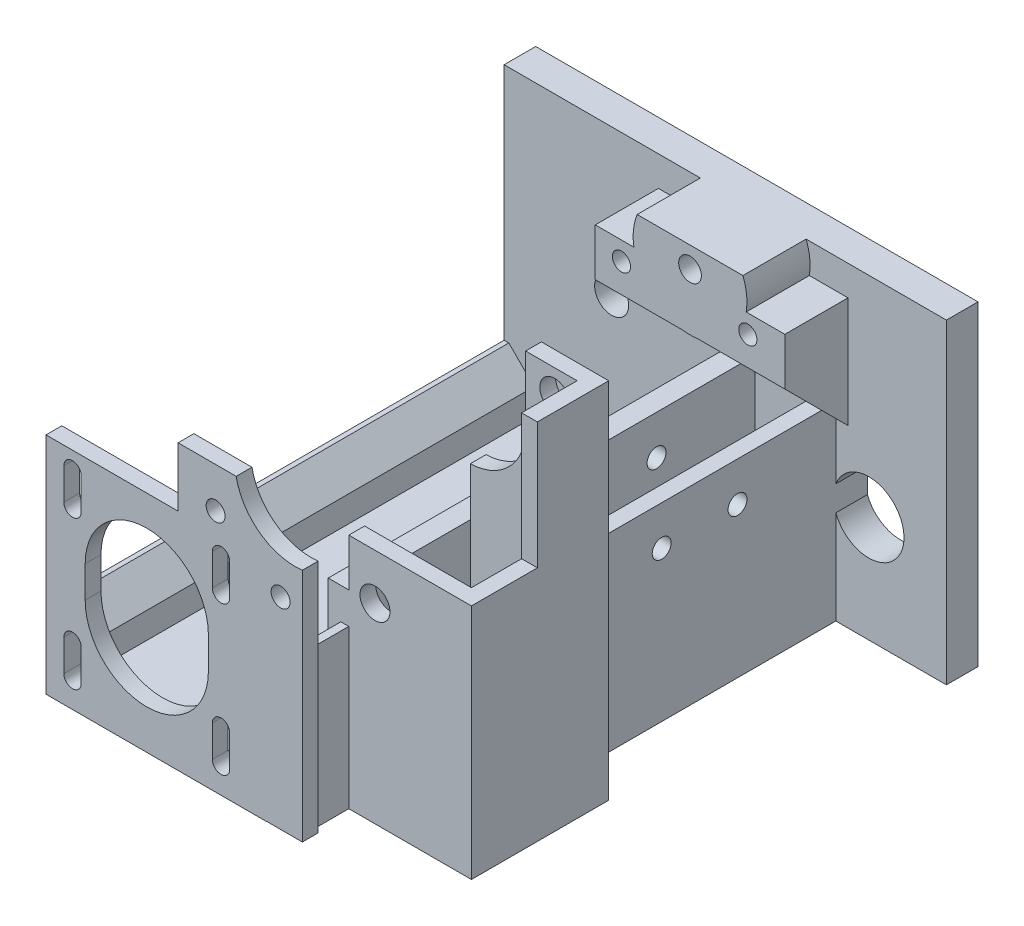
SolidWorks part; units mm, degrees
material "ABS"
ref_plane "Front Plane" through (0, 0, 0) normal (0, 0, 1) x (1, 0, 0)
ref_plane "Top Plane" through (0, 0, 0) normal (0, 1, 0) x (1, 0, 0)
ref_plane "Right Plane" through (0, 0, 0) normal (1, 0, 0) x (0, 0, -1)
sketch "Sketch1" plane through (0, 0, 0) normal (0, 0, 1) x (1, 0, 0)
  line L1 (-65.5446, 32.6733) -> (74.4554, 32.6733)
  line L2 (-65.5446, 32.6733) -> (-65.5446, -67.3267)
  line L3 (-65.5446, -67.3267) -> (74.4554, -67.3267)
  line L4 (74.4554, 32.6733) -> (74.4554, -67.3267)
  dimension "D1" = 100
  dimension "D2" = 140
extrude "Boss-Extrude1" add sketch "Sketch1" along normal blind 10
sketch "Sketch2" plane through (0, 0, 10) normal (0, 0, 1) x (1, 0, 0)
  line L0 (-65.5446, -67.3267) -> (-65.5446, -42.849)
  line L3 (-65.5446, -67.3267) -> (7.3151, -67.3267)
  line L5 (-65.5446, -67.3267) -> (74.4554, -67.3267) construction
  line L8 (-65.5446, 32.6733) -> (-65.5446, -67.3267) construction
  line L9 (-65.5446, -42.849) -> (-56.0483, -42.849)
  line L10 (-56.0483, -42.849) -> (-56.0483, -59.0904)
  line L11 (-56.0483, -59.0904) -> (7.3151, -59.0904)
  line L12 (7.3151, -59.0904) -> (7.3151, -7.3423)
  line L13 (7.3151, -7.3423) -> (13.8255, -7.3423)
  line L14 (13.8255, -7.3423) -> (13.8255, -67.3267)
  line L15 (13.8255, -67.3267) -> (7.3151, -67.3267)
extrude "Boss-Extrude2" add sketch "Sketch2" along normal blind 140
sketch "Sketch3" plane through (0, 0, 10) normal (0, 0, 1) x (1, 0, 0)
  line L1 (-16.6941, 23.1955) -> (43.3059, 23.1955)
  line L2 (-16.6941, 23.1955) -> (-16.6941, 8.1955)
  line L3 (-16.6941, 8.1955) -> (43.3059, 8.1955)
  line L4 (43.3059, 23.1955) -> (43.3059, 8.1955)
  dimension "D1" = 15
  dimension "D2" = 60
extrude "Boss-Extrude3" add sketch "Sketch3" along normal blind 20
sketch "Sketch4" plane through (0, 0, 10) normal (0, 0, 1) x (1, 0, 0)
  line L0 (43.3059, 8.1955) -> (43.3059, 23.1955) construction
  circle A0 centre (13.3059, 26.0432) radius 18
  dimension "D1" = 36
  dimension "D2" = 30
extrude "Boss-Extrude4" add sketch "Sketch4" along normal blind 20
sketch "Sketch6" plane through (0, 0, 30) normal (0, 0, 1) x (1, 0, 0)
  circle A0 centre (13.3059, 26.0432) radius 3.5973
  arc A1 (31.0792, 23.1955) -> (-4.4674, 23.1955) centre (13.3059, 26.0432) ccw construction
extrude "Cut-Extrude2" cut sketch "Sketch6" against normal blind 100
sketch "Sketch5" plane through (0, 0, 30) normal (0, 0, 1) x (1, 0, 0)
  line L0 (74.4554, 32.6733) -> (30.0404, 32.6733) construction
  line L1 (-13.303, 47.4) -> (34.4273, 47.4)
  line L2 (-13.303, 47.4) -> (-13.303, 32.6733)
  line L3 (-13.303, 32.6733) -> (34.4273, 32.6733)
  line L4 (34.4273, 47.4) -> (34.4273, 32.6733)
extrude "Cut-Extrude1" cut sketch "Sketch5" against normal blind 20
sketch "Sketch7" plane through (0, 0, 30) normal (0, 0, 1) x (1, 0, 0)
  circle A0 centre (-8.3949, 17.2978) radius 2.8779
extrude "Cut-Extrude3" cut sketch "Sketch7" against normal blind 100
pattern_linear "LPattern1" count 2 spacing 40 along (1, 0, 0) of "Cut-Extrude3"
sketch "Sketch9" plane through (0, 0, 150) normal (0, 0, 1) x (1, 0, 0)
  line L0 (-65.5446, 32.6733) -> (-65.5446, -42.849) construction
  line L1 (4.1877, 3.7072) -> (-65.5446, 3.7072)
  line L2 (4.1877, 3.7072) -> (4.1877, -67.3896)
  line L3 (4.1877, -67.3896) -> (-65.5446, -67.3896)
  line L4 (-65.5446, 3.7072) -> (-65.5446, -67.3896)
extrude "Boss-Extrude5" add sketch "Sketch9" along normal blind 5
chamfer "Chamfer1" distance 20 angle 45 2 edges at (29.4741, 8.1955, 10) (-2.8623, 8.1955, 10)
sketch "Sketch11" plane through (0, 0, 155) normal (0, 0, 1) x (1, 0, 0)
  line L0 (13.8255, -67.3267) -> (74.4554, -67.3267) construction
  line L1 (-23.7439, 22.4423) -> (15.6103, 22.4423)
  line L2 (-23.7439, 22.4423) -> (-23.7439, -67.3267)
  line L3 (-23.7439, -67.3267) -> (15.6103, -67.3267)
  line L4 (15.6103, 22.4423) -> (15.6103, -67.3267)
extrude "Boss-Extrude6" add sketch "Sketch11" against normal blind 5
sketch "Sketch12" plane through (0, 0, 155) normal (0, 0, 1) x (1, 0, 0)
  circle A0 centre (13.3059, 26.0432) radius 19
extrude "Cut-Extrude5" cut sketch "Sketch12" against normal blind 10
sketch "Sketch13" plane through (0, 0, 155) normal (0, 0, 1) x (1, 0, 0)
  circle A0 centre (-11.8599, 9.7129) radius 3
  circle A1 centre (8.7091, -3.6025) radius 3
  circle A2 centre (13.3059, 26.0432) radius 30 construction
  dimension "D1" = 6
  dimension "D2" = 6
extrude "Cut-Extrude6" cut sketch "Sketch13" against normal blind 10
fillet "Fillet2" radius 10 rebuild error yes
chamfer "Chamfer2" distance 8 angle 45 1 edges at (-56.0483, -42.849, 80)
sketch "Sketch14" plane through (0, 0, 10) normal (0, 0, 1) x (1, 0, 0)
  circle A0 centre (-31.5077, -13.6101) radius 5.3914
  circle A1 centre (49.8779, -33.6888) radius 11.1548
extrude "Cut-Extrude7" cut sketch "Sketch14" against normal blind 10
sketch "Sketch15" plane through (0, -67.3267, 0) normal (0, -1, 0) x (1, 0, 0)
  line L1 (4.5956, 95.0738) -> (52.6384, 95.0738)
  line L2 (4.5956, 95.0738) -> (4.5956, 138.5253)
  line L3 (4.5956, 138.5253) -> (52.6384, 138.5253)
  line L4 (52.6384, 95.0738) -> (52.6384, 138.5253)
extrude "Boss-Extrude7" add sketch "Sketch15" against normal blind 5
sketch "Sketch16" plane through (0, -62.3267, 0) normal (0, 1, 0) x (1, 0, 0)
  line L8 (13.8255, -133.5253) -> (13.8255, -138.5253)
  line L9 (13.8255, -138.5253) -> (13.8255, -95.0738) construction
  line L10 (13.8255, -138.5253) -> (52.6384, -138.5253)
  line L11 (52.6384, -138.5253) -> (52.6384, -116.7995)
  line L12 (52.6384, -95.0738) -> (52.6384, -138.5253) construction
  line L13 (52.6384, -116.7995) -> (47.6384, -116.7995)
  line L14 (47.6384, -116.7995) -> (47.6384, -133.5253)
  line L15 (47.6384, -133.5253) -> (13.8255, -133.5253)
  dimension "D1" = 5
  dimension "D2" = 5
extrude "Boss-Extrude8" add sketch "Sketch16" along normal blind 70
sketch "Sketch17" plane through (0, 7.6733, 0) normal (0, 1, 0) x (1, 0, 0)
  line L1 (28.8586, -179.0031) -> (38.4745, -179.0031)
  line L2 (28.8586, -179.0031) -> (28.8586, -197.9959)
  line L3 (28.8586, -197.9959) -> (38.4745, -197.9959)
  line L4 (38.4745, -179.0031) -> (38.4745, -197.9959)
extrude "Cut-Extrude8" cut sketch "Sketch17" against normal blind 20 rebuild error yes
sketch "Sketch18" plane through (0, 0, 138.5253) normal (0, 0, 1) x (1, 0, 0)
  circle A0 centre (22.1124, -6.8448) radius 4.75
  dimension "D1" = 9.5
extrude "Cut-Extrude9" cut sketch "Sketch18" against normal blind 20
sketch "Sketch19" plane through (0, -62.3267, 0) normal (0, 1, 0) x (1, 0, 0)
  line L0 (13.8199, -95.0738) -> (13.8199, -100.0738)
  line L3 (13.8199, -100.0738) -> (47.6384, -100.0738)
  line L6 (47.6384, -100.0738) -> (47.6384, -117.6475)
  line L7 (47.6384, -117.6475) -> (52.6384, -117.6475)
  line L8 (52.6384, -95.0738) -> (52.6384, -116.7995) construction
  line L9 (52.6384, -117.6475) -> (52.6384, -95.0738)
  line L10 (52.6384, -95.0738) -> (13.8199, -95.0738)
  dimension "D1" = 5
  dimension "D2" = 5
extrude "Boss-Extrude9" add sketch "Sketch19" along normal blind 110
sketch "Sketch20" plane through (0, 0, 100.0738) normal (0, 0, 1) x (1, 0, 0)
  line L0 (13.3059, 26.0432) -> (13.3059, 51.1413) construction
  line L1 (-4.7235, 26.0432) -> (-4.7235, 51.1413)
  line L2 (31.3354, 26.0432) -> (31.3354, 51.1413)
  arc A0 (-4.7235, 26.0432) -> (31.3354, 26.0432) centre (13.3059, 26.0432) ccw
  arc A1 (31.3354, 51.1413) -> (-4.7235, 51.1413) centre (13.3059, 51.1413) ccw
  point P3 (13.3059, 38.5923)
extrude "Cut-Extrude10" cut sketch "Sketch20" against normal blind 70
sketch "Sketch21" plane through (0, 0, 100.0738) normal (0, 0, 1) x (1, 0, 0)
  circle A0 centre (40.582, 40.031) radius 4.75
  dimension "D1" = 9.5
extrude "Cut-Extrude11" cut sketch "Sketch21" against normal blind 70
sketch "Sketch22" plane through (0, 0, 155) normal (0, 0, 1) x (1, 0, 0)
  line L0 (-57.1445, -58.9171) -> (-57.1445, -48.9171) construction
  line L1 (-59.8916, -58.9171) -> (-59.8916, -48.9171)
  line L2 (-54.3974, -58.9171) -> (-54.3974, -48.9171)
  line L3 (-33.6445, -35.4171) -> (-33.6445, -25.4171) construction
  line L4 (-53.1445, -35.4171) -> (-53.1445, -25.4171)
  line L5 (-14.1445, -35.4171) -> (-14.1445, -25.4171)
  line L6 (-10.1445, -58.9171) -> (-10.1445, -48.9171) construction
  line L7 (-12.8916, -58.9171) -> (-12.8916, -48.9171)
  line L8 (-7.3974, -58.9171) -> (-7.3974, -48.9171)
  line L9 (-10.1445, -11.9171) -> (-10.1445, -1.9171) construction
  line L10 (-12.8916, -11.9171) -> (-12.8916, -1.9171)
  line L11 (-7.3974, -11.9171) -> (-7.3974, -1.9171)
  line L12 (-57.1445, -11.9171) -> (-57.1445, -1.9171) construction
  line L13 (-59.8916, -11.9171) -> (-59.8916, -1.9171)
  line L14 (-54.3974, -11.9171) -> (-54.3974, -1.9171)
  arc A0 (-59.8916, -58.9171) -> (-54.3974, -58.9171) centre (-57.1445, -58.9171) ccw
  arc A1 (-54.3974, -48.9171) -> (-59.8916, -48.9171) centre (-57.1445, -48.9171) ccw
  arc A2 (-53.1445, -35.4171) -> (-14.1445, -35.4171) centre (-33.6445, -35.4171) ccw
  arc A3 (-14.1445, -25.4171) -> (-53.1445, -25.4171) centre (-33.6445, -25.4171) ccw
  arc A4 (-12.8916, -58.9171) -> (-7.3974, -58.9171) centre (-10.1445, -58.9171) ccw
  arc A5 (-7.3974, -48.9171) -> (-12.8916, -48.9171) centre (-10.1445, -48.9171) ccw
  arc A6 (-12.8916, -11.9171) -> (-7.3974, -11.9171) centre (-10.1445, -11.9171) ccw
  arc A7 (-7.3974, -1.9171) -> (-12.8916, -1.9171) centre (-10.1445, -1.9171) ccw
  arc A8 (-59.8916, -11.9171) -> (-54.3974, -11.9171) centre (-57.1445, -11.9171) ccw
  arc A9 (-54.3974, -1.9171) -> (-59.8916, -1.9171) centre (-57.1445, -1.9171) ccw
  point P2 (-57.1445, -53.9171)
  point P9 (-33.6445, -30.4171)
  point P16 (-10.1445, -53.9171)
  point P23 (-10.1445, -6.9171)
  point P30 (-57.1445, -6.9171)
  dimension "D5" = 19.5
  dimension "D1" = 10
  dimension "D2" = 10
  dimension "D3" = 23.5
  dimension "D4" = 23.5
extrude "Cut-Extrude12" cut sketch "Sketch22" against normal blind 10
sketch "Sketch23" plane through (7.3151, 0, 0) normal (-1, 0, 0) x (0, 0, 1)
  line L0 (150, 3.7072) -> (150, -42.849) construction
  line L1 (138.5253, -7.3423) -> (150, -7.3423)
  line L2 (138.5253, -7.3423) -> (138.5253, -17.3423)
  line L3 (138.5253, -17.3423) -> (150, -17.3423)
  line L4 (150, -7.3423) -> (150, -17.3423)
  dimension "D1" = 10
extrude "Cut-Extrude13" cut sketch "Sketch23" against normal blind 10
chamfer "Chamfer4" distance 4 angle 45 1 edges at (7.3151, -17.3423, 144.2627)
sketch "Sketch24" plane through (0, -67.3267, 0) normal (0, -1, 0) x (1, 0, 0)
  line L0 (-65.5446, 0) -> (74.4554, 0) construction
  line L1 (39.4554, 0) -> (34.4554, 0)
  line L2 (39.4554, 0) -> (39.4554, 106.4381)
  line L3 (39.4554, 106.4381) -> (34.4554, 106.4381)
  line L4 (34.4554, 0) -> (34.4554, 106.4381)
  line L5 (74.4554, 10) -> (74.4554, 0) construction
  dimension "D1" = 5
  dimension "D2" = 35
extrude "Boss-Extrude10" add sketch "Sketch24" against normal blind 60
sketch "Sketch25" plane through (39.4554, 0, 0) normal (1, 0, 0) x (0, 0, -1)
  circle A0 centre (-65.1201, -19.8217) radius 3
extrude "Cut-Extrude14" cut sketch "Sketch25" against normal blind 60
pattern_linear "LPattern2" count 2 spacing 24 along (0, 0, -1) of "Cut-Extrude14"
